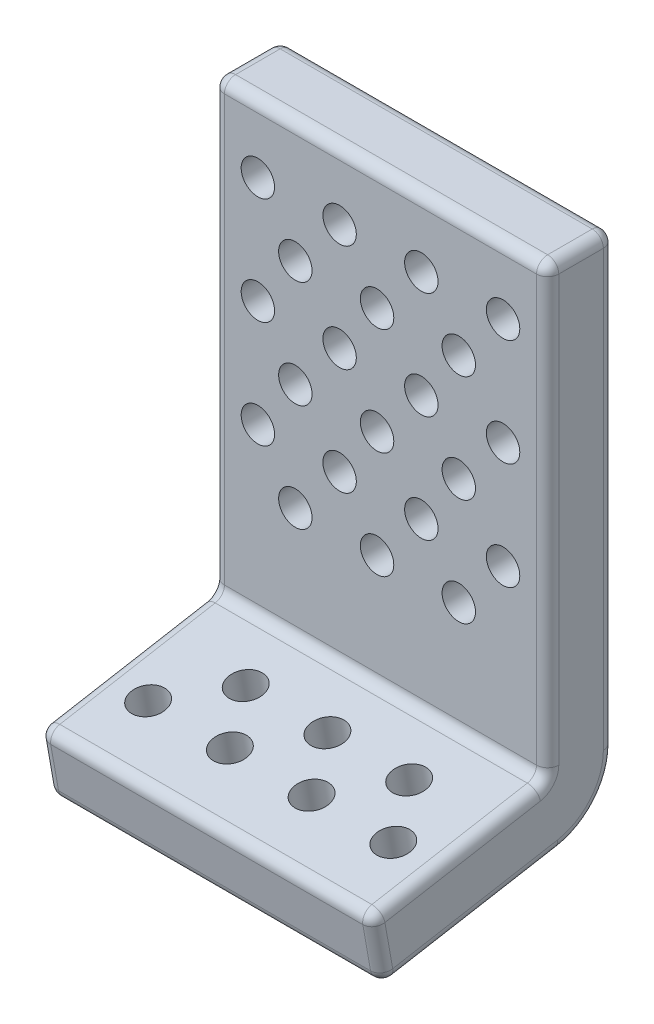
SolidWorks part; units mm, degrees
ref_plane "Спереди" through (0, 0, 0) normal (0, 0, 1) x (1, 0, 0)
ref_plane "Сверху" through (0, 0, 0) normal (0, 1, 0) x (1, 0, 0)
ref_plane "Справа" through (0, 0, 0) normal (1, 0, 0) x (0, 0, -1)
sketch "Эскиз1" plane through (0, 0, 0) normal (1, 0, 0) x (0, 0, -1)
  line L1 (0, 0) -> (-3, 0)
  line L2 (0, 0) -> (0, -20)
  line L4 (-3, 0) -> (-3, -20)
  line L7 (-3, -20) -> (-10.8785, -21.3892)
  line L8 (-10.8785, -21.3892) -> (-10.3575, -24.3436)
  line L9 (-10.3575, -24.3436) -> (-2.4791, -22.9544)
  arc A2 (0, -20) -> (-2.4791, -22.9544) centre (-3, -20) cw
  point P7 (0, 0)
  dimension "D5" = 3
  dimension "D2" = 80
  dimension "D4" = 3
  dimension "D1" = 3
  dimension "D3" = 8
  dimension "D6" = 20
extrude "Бобышка-Вытянуть1" add sketch "Эскиз1" along normal blind 15
sketch "Эскиз2" plane through (0, 0, 3) normal (0, 0, 1) x (1, 0, 0)
  circle A0 centre (2, -3) radius 0.75
  circle A1 centre (5.6667, -3) radius 0.75
  circle A2 centre (9.3333, -3) radius 0.75
  circle A3 centre (13, -3) radius 0.75
  circle A4 centre (3.6805, -5.4) radius 0.75
  circle A5 centre (7.3472, -5.4) radius 0.75
  circle A6 centre (11.0138, -5.4) radius 0.75
  circle A7 centre (2, -7.8) radius 0.75
  circle A8 centre (5.6667, -7.8) radius 0.75
  circle A9 centre (3.6805, -10.2) radius 0.75
  circle A10 centre (7.3472, -10.2) radius 0.75
  circle A11 centre (9.3333, -7.8) radius 0.75
  circle A12 centre (11.0138, -10.2) radius 0.75
  circle A13 centre (13, -7.8) radius 0.75
  circle A14 centre (2, -12.6) radius 0.75
  circle A15 centre (5.6667, -12.6) radius 0.75
  circle A16 centre (3.6805, -15) radius 0.75
  circle A17 centre (7.3472, -15) radius 0.75
  circle A18 centre (9.3333, -12.6) radius 0.75
  circle A19 centre (11.0138, -15) radius 0.75
  circle A20 centre (13, -12.6) radius 0.75
  dimension "D3" = 1.5
  dimension "D1" = 2
  dimension "D2" = 3
  dimension "D5" = 2
  dimension "D7" = 2.4
  dimension "D9" = 2.4
  dimension "D11" = 2.4
  dimension "D4" = 4
  dimension "D6" = 2
  dimension "D8" = 2
  dimension "D10" = 2
sketch "Эскиз3" plane through (0, -23.2681, 21.5346) normal (0, -0.9848, -0.1736) x (1, 0, 0)
  circle A0 centre (2, -13.8205) radius 0.75
  circle A1 centre (5.6667, -13.8205) radius 0.75
  circle A2 centre (9.3333, -13.8205) radius 0.75
  circle A3 centre (13, -13.8205) radius 0.75
  circle A4 centre (4.0138, -16.2205) radius 0.75
  circle A5 centre (7.6805, -16.2205) radius 0.75
  circle A6 centre (11.3472, -16.2205) radius 0.75
  point P23 (2, -14.065)
  point P24 (2, -13.5616)
  dimension "D1" = 1.5
  dimension "D2" = 3
  dimension "D3" = 2
  dimension "D5" = 2
  dimension "D7" = 2.4
  dimension "D4" = 4
  dimension "D6" = 2
extrude "Вырез-Вытянуть1" cut sketch "Эскиз2" against normal blind 15
extrude "Вырез-Вытянуть2" cut sketch "Эскиз3" along normal blind 15
extrude "Вырез-Вытянуть3" cut sketch "Эскиз2<2>" against normal blind 1 draft 60 from offset 2.7 draft outward yes offset against normal yes
sketch "Эскиз2<2>" plane through (0, 0, 3) normal (0, 0, 1) x (1, 0, 0) same geometry as "Эскиз2"
extrude "Вырез-Вытянуть4" cut sketch "Эскиз3<2>" along normal blind 1 draft 60 from offset 2.7 draft outward yes
sketch "Эскиз3<2>" plane through (0, -23.2681, 21.5346) normal (0, -0.9848, -0.1736) x (1, 0, 0) same geometry as "Эскиз3"
fillet "Скругление1" radius 0.5 19 edges at (0, -10, 0) (15, -10, 0) (15, 0, 1.5) (7.5, 0, 0) (0, -10, 3) (7.5, 0, 3) (15, -10, 3) (0, -23.649, 6.4183) (0, -21.9284, 0.7019) (15, -23.649, 6.4183) (15, -21.9284, 0.7019) (0, 0, 1.5) (0, -22.8664, 10.618) (15, -22.8664, 10.618) (7.5, -24.3436, 10.3575) (7.5, -21.3892, 10.8785) (0, -20.6946, 6.9392) (15, -20.6946, 6.9392) (7.5, -20, 3)
